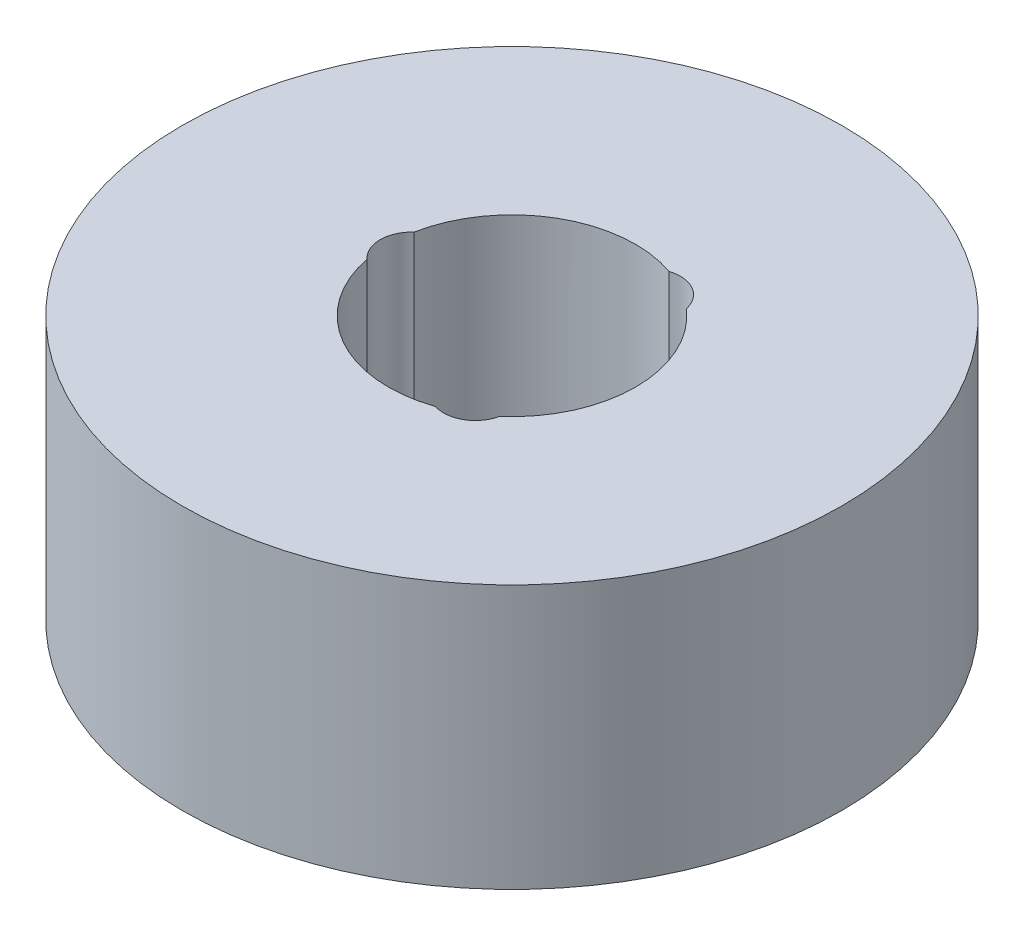
SolidWorks part; units mm, degrees
ref_plane "Front Plane" through (0, 0, 0) normal (0, 0, 1) x (1, 0, 0)
ref_plane "Top Plane" through (0, 0, 0) normal (0, 1, 0) x (1, 0, 0)
ref_plane "Right Plane" through (0, 0, 0) normal (1, 0, 0) x (0, 0, -1)
sketch "Sketch1" plane through (0, 0, 0) normal (0, 1, 0) x (1, 0, 0)
  circle A0 centre (0, 0) radius 20
  dimension "FLANGE_OD" = 40
extrude "Boss-Extrude1" add sketch "Sketch1" along normal blind 16
sketch "Sketch2" plane through (0, 0, 0) normal (0, 1, 0) x (1, 0, 0)
  circle A0 centre (0, 0) radius 7.5
  dimension "BORE_D" = 15
extrude "Cut-Extrude1" cut sketch "Sketch2" along normal through all
sketch "Sketch3" plane through (0, 16, 0) normal (0, 1, 0) x (1, 0, 0)
  circle A0 centre (0, 0) radius 6.0673 construction
  circle A1 centre (-6.0673, 0) radius 1.9282
  dimension "BOLT_D" = 3.8565
  dimension "BOLT_PCD" = 12.1347
extrude "Cut-Extrude2" cut sketch "Sketch3" against normal blind 9.8144
pattern_circular "CirPattern1" count 3 over 360 about axis through (0, 0, 0) along (0, 1, 0) of "Cut-Extrude2"
